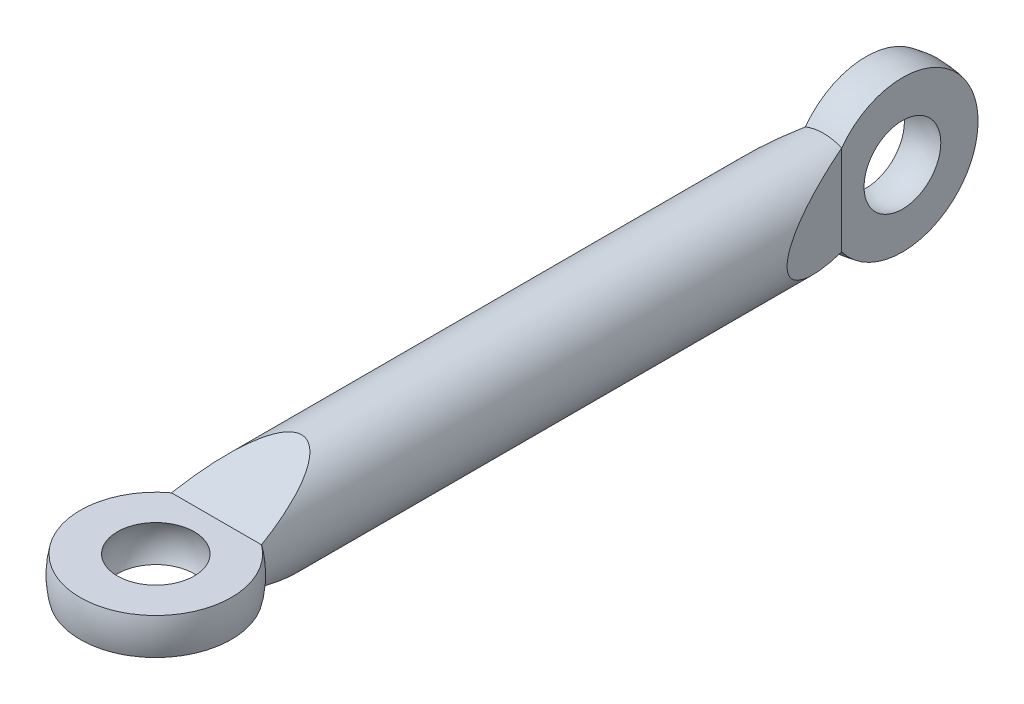
SolidWorks part; units mm, degrees
ref_plane "前视基准面" through (0, 0, 0) normal (0, 0, 1) x (1, 0, 0)
ref_plane "上视基准面" through (0, 0, 0) normal (0, 1, 0) x (1, 0, 0)
ref_plane "右视基准面" through (0, 0, 0) normal (1, 0, 0) x (0, 0, -1)
sketch "草图1" plane through (0, 0, 0) normal (0, 0, 1) x (1, 0, 0)
  circle A0 centre (0, 0) radius 4
  dimension "D1" = 8
extrude "凸台-拉伸1" add sketch "草图1" along normal mid plane 50
sketch "草图2" plane through (0, 0, 0) normal (0, 1, 0) x (1, 0, 0)
  line L0 (0, 36.4031) -> (0, 23.5969)
  line L1 (0, 0) -> (-4, 0) construction
  line L2 (-4, 25) -> (-4, -25) construction
  line L3 (0, -36.4031) -> (0, -23.5969)
  circle A0 centre (0, 30) radius 3.5
  circle A1 centre (0, 30) radius 6.4031
  circle A2 centre (0, -30) radius 6.4031
  circle A3 centre (0, -30) radius 3.5
  dimension "D1" = 30
  dimension "D2" = 7
revolve "旋转2" add sketch "草图2" angle 360 about L0 region at (4.4265, 0, -34.4265) region at (0.1432, 0, 34.9516)
sketch "草图3" plane through (0, 0, 0) normal (1, 0, 0) x (0, 0, -1)
  line L0 (0, 0) -> (-25, 0) construction
  line L1 (-25, 4) -> (-25, -4) construction
  line L2 (-18, 4) -> (-25, 1.5)
  line L3 (25, 4) -> (-25, 4) construction
  line L4 (-25, 1.5) -> (-38, 1.5)
  line L5 (-38, 1.5) -> (-38, 8)
  line L6 (-38, 8) -> (-18, 8)
  line L7 (-18, 8) -> (-18, 4)
  line L8 (-18, -8) -> (-18, -4)
  line L9 (-38, -8) -> (-18, -8)
  line L10 (-38, -1.5) -> (-38, -8)
  line L11 (-25, -1.5) -> (-38, -1.5)
  line L12 (-18, -4) -> (-25, -1.5)
  dimension "D1" = 18
  dimension "D2" = 20
  dimension "D3" = 6.5
  dimension "D4" = 4
extrude "切除-拉伸1" cut sketch "草图3" against normal through all both and the other way through all
sketch "草图4" plane through (0, 0, 0) normal (0, 1, 0) x (1, 0, 0)
  line L0 (0, 0) -> (0, 25) construction
  line L1 (4, 25) -> (-4, 25) construction
  line L2 (4, 18) -> (1.5, 25)
  line L3 (4, -25) -> (4, 25) construction
  line L4 (1.5, 25) -> (1.5, 39)
  line L5 (1.5, 39) -> (8, 39)
  line L6 (8, 39) -> (8, 18)
  line L7 (8, 18) -> (4, 18)
  line L8 (-8, 18) -> (-4, 18)
  line L9 (-8, 39) -> (-8, 18)
  line L10 (-1.5, 39) -> (-8, 39)
  line L11 (-1.5, 25) -> (-1.5, 39)
  line L12 (-4, 18) -> (-1.5, 25)
  dimension "D1" = 18
  dimension "D2" = 4
  dimension "D3" = 6.5
  dimension "D4" = 14
extrude "切除-拉伸2" cut sketch "草图4" against normal through all both and the other way through all
